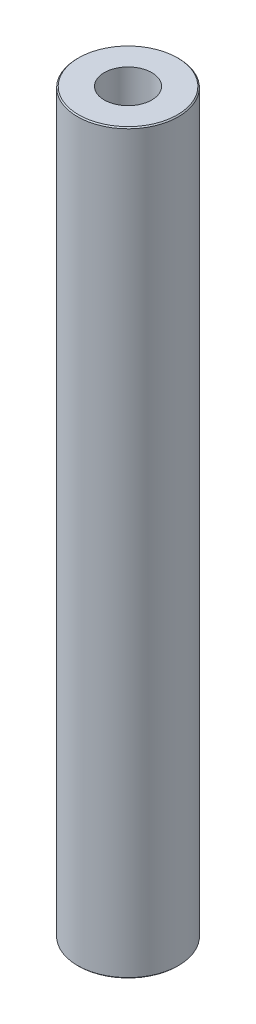
SolidWorks part; units mm, degrees
ref_plane "Front Plane" through (0, 0, 0) normal (0, 0, 1) x (1, 0, 0)
ref_plane "Top Plane" through (0, 0, 0) normal (0, 1, 0) x (1, 0, 0)
ref_plane "Right Plane" through (0, 0, 0) normal (1, 0, 0) x (0, 0, -1)
sketch "Sketch1" plane through (0, 0, 0) normal (0, 1, 0) x (1, 0, 0)
  circle A0 centre (0, 0) radius 40
  dimension "SHAFT_OD" = 80
extrude "Boss-Extrude1" add sketch "Sketch1" along normal blind 583.9476
sketch "Sketch2" plane through (0, 0, 0) normal (0, 1, 0) x (1, 0, 0)
  circle A0 centre (0, 0) radius 18.8191
  dimension "BORE_D" = 37.6381
extrude "Cut-Extrude1" cut sketch "Sketch2" along normal through all
chamfer "Chamfer1" distance 0.8718 angle 45 2 edges at (0, 583.9476, 40) (0, 0, 40)
